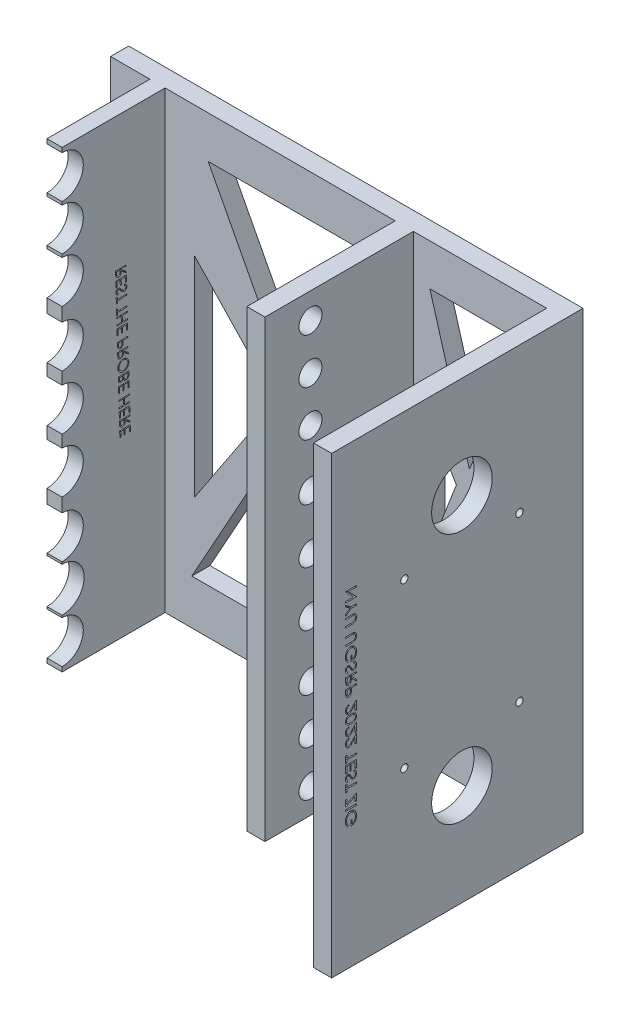
SolidWorks part; units mm, degrees
ref_plane "Front Plane" through (0, 0, 0) normal (0, 0, 1) x (1, 0, 0)
ref_plane "Top Plane" through (0, 0, 0) normal (0, 1, 0) x (1, 0, 0)
ref_plane "Right Plane" through (0, 0, 0) normal (1, 0, 0) x (0, 0, -1)
sketch "Sketch1" plane through (0, 0, 0) normal (0, 0, 1) x (1, 0, 0)
  line L1 (75, -75) -> (-75, -75)
  line L2 (75, -75) -> (75, 75)
  line L3 (75, 75) -> (-75, 75)
  line L4 (-75, -75) -> (-75, 75)
  line L5 (75, -75) -> (-75, 75) construction
  line L6 (75, 75) -> (-75, -75) construction
  line L7 (69, -75) -> (75, -75)
  line L8 (69, -75) -> (69, 75)
  line L9 (69, 75) -> (75, 75)
  line L10 (75, -75) -> (75, 75)
  line L11 (25, -75) -> (19, -75)
  line L12 (25, -75) -> (25, 75)
  line L13 (25, 75) -> (19, 75)
  line L14 (19, -75) -> (19, 75)
  line L15 (-57, -75) -> (-62, -75)
  line L16 (-57, -75) -> (-57, 75)
  line L17 (-57, 75) -> (-62, 75)
  line L18 (-62, -75) -> (-62, 75)
  point P0 (0, 0)
  point P7 (0, 75)
  point P19 (-62, 75)
  dimension "D1" = 150
  dimension "D2" = 150
  dimension "D3" = 6
  dimension "D4" = 0
  dimension "D5" = 13
  dimension "D6" = 5
  dimension "D7" = 76
  dimension "D8" = 6
extrude "Boss-Extrude3" add sketch "Sketch1" against normal blind 6 contours L3 L4 L1 L2
extrude "Boss-Extrude4" add sketch "Sketch1<5>" along normal blind 49 contours L14 L1 L12 L3 region at (22, 0, 0)
sketch "Sketch1<5>" plane through (0, 0, 0) normal (0, 0, 1) x (1, 0, 0) same geometry as "Sketch1"
extrude "Boss-Extrude5" add sketch "Sketch1<6>" along normal blind 77 contours L1 L10 L3 L8 region at (72, 0, 0)
sketch "Sketch1<6>" plane through (0, 0, 0) normal (0, 0, 1) x (1, 0, 0) same geometry as "Sketch1"
extrude "Boss-Extrude6" add sketch "Sketch1<7>" along normal blind 34 contours L18 L17 L16 L15
sketch "Sketch1<7>" plane through (0, 0, 0) normal (0, 0, 1) x (1, 0, 0) same geometry as "Sketch1"
sketch "Sketch3" plane through (-62, 0, 0) normal (-1, 0, 0) x (0, 0, 1)
  line L0 (12.8961, 31.2924) -> (11.0191, -32.0016) construction
  line L2 (34, -75) -> (34, 75) construction
  circle A0 centre (34, 0) radius 7
  circle A1 centre (34, 36.5) radius 7
  circle A2 centre (34, -36.5) radius 7
  circle A3 centre (34, 18) radius 7
  circle A4 centre (34, -18) radius 7
  circle A5 centre (34, 51.5) radius 7
  circle A6 centre (34, -51.5) radius 7.2855
  circle A7 centre (34, 66.5) radius 7
  circle A8 centre (34, -66.5) radius 7
  text T0 "REST THE PROBE HERE"
  dimension "D1" = 36.5
  dimension "D3" = 18
  dimension "D5" = 15
  dimension "D2" = 36.5
  dimension "D4" = 18
  dimension "D6" = 15
  dimension "D7" = 15
  dimension "D8" = 15
extrude "Cut-Extrude5" cut sketch "Sketch3" against normal blind 35
sketch "Sketch4" plane through (69, 0, 0) normal (-1, 0, 0) x (0, 0, 1)
  line L0 (77, -75) -> (77, 75) construction
  line L1 (53, 41.5) -> (53, -41.5) construction
  line L2 (68.8756, 41.5) -> (68.8756, -41.5) construction
  line L5 (77, 0) -> (3.3451, 0) construction
  circle A0 centre (34, 41.5) radius 10
  circle A1 centre (34, -41.5) radius 10
  text T0 "     NYU UGSRP 2022 TEST ZIG" font "Century Gothic" height 3.5
  point P6 (53, 27)
  point P7 (53, -27)
  point P8 (15, -27)
  point P9 (15, 27)
  dimension "D1" = 20
  dimension "D8" = 14.5
  dimension "D2" = 27
  dimension "D3" = 27
  dimension "D4" = 19
  dimension "D5" = 19
  dimension "D6" = 14.5
  dimension "D7" = 27
extrude "Cut-Extrude6" cut sketch "Sketch4" against normal blind 80
hole_wizard "M2 Clearance Hole3" positions "3DSketch1" profile "Sketch14" hole size "M2" standard "ANSI Metric" end condition through all
sketch3d "3DSketch1"
  point P0 (69, 27, 53)
  point P3 (69, -27, 53)
  point P6 (69, 27, 15)
sketch "Sketch14" plane through (69, 27, 53) normal (0, 1, 0) x (0, 0, 1)
  line L0 (0, 0) -> (0, 6)
  line L1 (0, 6) -> (1.2, 6)
  line L2 (1.2, 6) -> (1.2, 0.025)
  line L3 (1.2, 0.025) -> (1.225, 0)
  line L5 (1.225, 0) -> (0, 0)
  line L6 (-1.2, 0.025) -> (-1.225, 0) construction
  line L11 (0, -6.35) -> (0, 107.95) construction
  dimension "Thru Hole Dia." = 2.4
  dimension "Thru Hole Depth" = 6
  dimension "Near C'Sink Dia." = 2.45
  dimension "Near C'Sink Angle" = 90
hole_wizard "M2 Clearance Hole4" positions "3DSketch3" profile "Sketch16" hole size "M2" standard "ANSI Metric" end condition through all
sketch3d "3DSketch3"
  point P0 (69, -27, 15)
sketch "Sketch16" plane through (69, -27, 15) normal (0, 1, 0) x (0, 0, 1)
  line L0 (0, 0) -> (0, 6)
  line L1 (0, 6) -> (1.2, 6)
  line L2 (1.2, 6) -> (1.2, 0.025)
  line L3 (1.2, 0.025) -> (1.225, 0)
  line L5 (1.225, 0) -> (0, 0)
  line L6 (-1.2, 0.025) -> (-1.225, 0) construction
  line L11 (0, -6.35) -> (0, 107.95) construction
  dimension "Thru Hole Dia." = 2.4
  dimension "Thru Hole Depth" = 6
  dimension "Near C'Sink Dia." = 2.45
  dimension "Near C'Sink Angle" = 90
sketch "Sketch17" plane through (0, 0, 0) normal (0, 0, 1) x (1, 0, 0)
  line L1 (-73.3562, -72.2727) -> (-63.8016, -72.2727)
  line L2 (-73.3562, -72.2727) -> (-73.3562, 72.6914)
  line L3 (-73.3562, 72.6914) -> (-63.8016, 72.6914)
  line L4 (-63.8016, -72.2727) -> (-63.8016, 72.6914)
sketch "Sketch22" plane through (19, 0, 0) normal (-1, 0, 0) x (0, 0, 1)
  line L1 (49, 75) -> (0, 75) construction
  circle A0 centre (34, 66.5) radius 3.8
  circle A1 centre (34, 51.5) radius 3.8
  circle A2 centre (34, -18) radius 3.8
  circle A3 centre (34, 36.5) radius 3.8
  circle A4 centre (34, 18) radius 3.8
  circle A5 centre (34, 0) radius 3.8
  circle A7 centre (34, -36.5) radius 3.8
  circle A8 centre (34, -51.5) radius 3.8
  circle A9 centre (34, -66.5) radius 3.8
  dimension "D1" = 7.6
  dimension "D2" = 75
  dimension "D3" = 18
  dimension "D4" = 18.5
  dimension "D5" = 15
  dimension "D6" = 15
  dimension "D7" = 18
  dimension "D8" = 18.5
  dimension "D9" = 15
  dimension "D10" = 15
extrude "Cut-Extrude7" cut sketch "Sketch22" against normal blind 10
sketch "Sketch23" plane through (0, 0, 0) normal (0, 0, 1) x (1, 0, 0)
  line L0 (-47.2694, -37.1669) -> (-47.2694, 31.8625)
  line L1 (-47.2694, 31.8625) -> (-20.3361, 3.4993)
  line L2 (-20.3361, 3.4993) -> (-47.2694, -37.1669)
  line L3 (-42.7796, 61.1232) -> (12.4506, 61.1232)
  line L4 (12.4506, 61.1232) -> (-16.0355, 10.1353)
  line L5 (-16.0355, 10.1353) -> (-42.7796, 61.1232)
  line L6 (-48.1795, -60.1626) -> (-16.0355, -2.2854)
  line L7 (-16.0355, -2.2854) -> (14.5336, -60.1626)
  line L8 (14.5336, -60.1626) -> (-48.1795, -60.1626)
  line L9 (14.7998, 31.4304) -> (-11.502, 3.8127)
  line L10 (-11.502, 3.8127) -> (14.7998, -36.6878)
  line L11 (14.7998, -36.6878) -> (14.7998, 31.4304)
  point P12 (13.1917, 62.4496)
  point P13 (-42.7796, 61.1232)
extrude "Cut-Extrude9" cut sketch "Sketch23" against normal blind 10
sketch "Sketch27" plane through (0, 0, 0) normal (0, 0, 1) x (1, 0, 0)
  line L0 (29.4764, -15.4313) -> (29.4764, 25.8378)
  line L1 (29.4764, 25.8378) -> (39.1776, 9.563)
  line L2 (39.1776, 9.563) -> (29.4764, -15.4313)
  line L3 (30.438, 61.29) -> (62.1781, 61.29)
  line L4 (62.1781, 61.29) -> (43.4782, 16.199)
  line L5 (43.4782, 16.199) -> (30.438, 61.29)
  line L6 (29.4764, -57.8735) -> (43.4782, 3.7783)
  line L7 (43.4782, 3.7783) -> (65.1915, -57.8735)
  line L8 (65.1915, -57.8735) -> (29.4764, -57.8735)
  line L9 (62.8166, 41.2956) -> (48.0117, 9.8764)
  line L10 (48.0117, 9.8764) -> (62.8166, -15.4313)
  line L11 (62.8166, -15.4313) -> (62.8166, 41.2956)
  point P12 (62.8166, 62.8296)
  point P13 (29.4764, 64.6151)
  point P14 (62.8166, -51.1304)
  point P15 (29.4764, -57.8735)
extrude "Cut-Extrude10" cut sketch "Sketch27" against normal blind 10
